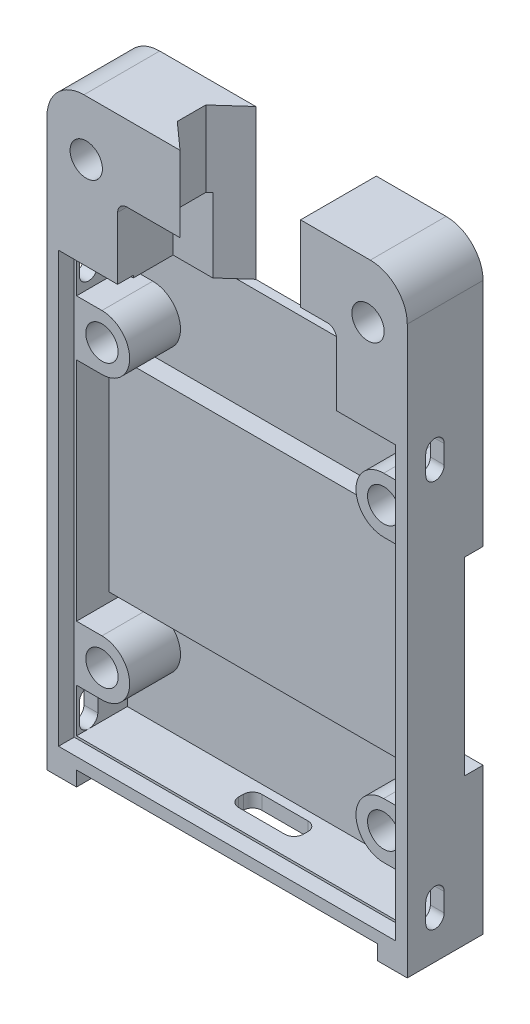
SolidWorks part; units mm, degrees
ref_plane "Front Plane" through (0, 0, 0) normal (0, 0, 1) x (1, 0, 0)
ref_plane "Top Plane" through (0, 0, 0) normal (0, 1, 0) x (1, 0, 0)
ref_plane "Right Plane" through (0, 0, 0) normal (1, 0, 0) x (0, 0, -1)
sketch "Sketch1" plane through (0, 0, 0) normal (0, 0, 1) x (1, 0, 0)
  line L0 (15.25, -20.35) -> (18, -20.35)
  line L1 (-19.5, -32.6) -> (19.5, -32.6)
  line L2 (-19.5, -32.6) -> (-19.5, 31.1)
  line L3 (-19.5, 31.1) -> (19.5, 31.1)
  line L4 (19.5, -32.6) -> (19.5, 31.1)
  line L5 (-15.25, -20.35) -> (-18, -20.35)
  line L6 (15.25, -26.35) -> (18, -26.35)
  line L7 (15.5, 31.1) -> (-15.5, 31.1) construction
  line L8 (-18, -31.1) -> (-18, 29.6)
  line L9 (-18, 29.6) -> (18, 29.6)
  line L10 (18, -31.1) -> (18, 29.6)
  line L11 (-18, -31.1) -> (18, -31.1)
  line L12 (-18, 14.9) -> (18, 14.9)
  line L13 (7.85, 14.9) -> (-4.95, 14.9) construction
  line L14 (-15.25, 4.15) -> (-18, 4.15)
  line L15 (-15.25, 10.15) -> (-18, 10.15)
  line L16 (15.25, 10.15) -> (18, 10.15)
  line L17 (15.25, 4.15) -> (18, 4.15)
  line L18 (-15.25, -26.35) -> (-18, -26.35)
  line L19 (19.5, -34.2) -> (19.5, -18.35) construction
  line L20 (-19.5, -34.2) -> (-19.5, -18.35) construction
  line L21 (15.3, -32.6) -> (-15.3, -32.6) construction
  arc A0 (19.5, 27.1) -> (15.5, 31.1) centre (15.5, 27.1) ccw construction
  arc A1 (-15.5, 31.1) -> (-19.5, 27.1) centre (-15.5, 27.1) ccw construction
  arc A2 (19.5, 27.1) -> (15.5, 31.1) centre (15.5, 27.1) ccw
  arc A3 (-15.5, 31.1) -> (-19.5, 27.1) centre (-15.5, 27.1) ccw
  arc A4 (-15.5, 29.6) -> (-18, 27.1) centre (-15.5, 27.1) ccw
  arc A5 (18, 27.1) -> (15.5, 29.6) centre (15.5, 27.1) ccw
  circle A6 centre (-15.25, -23.35) radius 1.75
  circle A7 centre (15.25, -23.35) radius 1.75
  circle A8 centre (-15.25, 7.15) radius 1.75
  circle A9 centre (15.25, 7.15) radius 1.75
  circle A10 centre (15.25, 25.15) radius 1.75
  circle A11 centre (-15.25, 25.15) radius 1.75
  circle A12 centre (-15.25, -23.35) radius 3
  circle A13 centre (15.25, -23.35) radius 3
  circle A14 centre (15.25, 7.15) radius 3
  circle A15 centre (-15.25, 7.15) radius 3
  point P46 (0, 0)
  point P69 (0, 0)
  point P72 (0, 0)
  dimension "D2" = 1.5
  dimension "D4" = 6
  dimension "D3" = 3.5
  dimension "D1" = 1.5
extrude "Base shape" add sketch "Sketch1" along normal up to surface (8.2 mm away) contours L10 A5 L9 A4 L8 L12 A11 A10 | L3 A3 L2 L1 L4 A2 A15 L8 L9 L10 A14 A13 L11 A12 | A4 L9 L8 | A5 L10 L9 | A15 L15 L8 | A15 L8 A8 | A15 L8 L14 | L8 A15 | A14 L17 L10 | L10 A14 A9 | L10 A14 | A14 L10 L16 | A13 L6 L10 | L10 A13 A7 | L10 A13 | A13 L10 L0 | A12 L8 L18 | A12 L8 A6 | L8 A12 | A12 L5 L8 region at (16.8481, -20.9099, 0) region at (17.3601, -20.8437, 0) region at (17.3601, -25.8563, 0) region at (18.1004, -23.35, 0) region at (17.3601, 4.6437, 0) region at (16.8481, 4.7099, 0) region at (18.1004, 7.15, 0) region at (17.3601, 9.6563, 0) region at (-17.3601, -25.8563, 0) region at (0, 22.1041, 0) region at (-18.1004, -23.35, 0) region at (-17.9169, -23.35, 0) region at (17.4416, 29.0416, 0) region at (-17.3601, -20.8437, 0) region at (-17.3601, 9.6563, 0) region at (-17.4416, 29.0416, 0) region at (-16.8481, 9.5901, 0) region at (-18.1004, 7.15, 0) region at (-17.3601, 4.6437, 0) region at (-18.7531, -2.75, 0)
sketch "Sketch3" plane through (19.5, 0, 0) normal (1, 0, 0) x (0, 0, -1)
  line L1 (0, -18.35) -> (-2, -18.35)
  line L2 (0, -18.35) -> (0, 2.15)
  line L3 (0, 2.15) -> (-2, 2.15)
  line L4 (-2, -18.35) -> (-2, 2.15)
  line L5 (0, -18.35) -> (2, -18.35) construction
  line L6 (0, 2.15) -> (2, 2.15) construction
  line L7 (0, -32.6) -> (0, 27.1) construction
  dimension "D1" = 2
extrude "Strap cut" cut sketch "Sketch3" against normal through all
sketch "Sketch4" plane through (0, 31.1, 0) normal (0, 1, 0) x (1, 0, 0)
  line L2 (7.95, 0) -> (-5.0998, 0)
  line L4 (-15.5, 0) -> (15.5, 0) construction
  line L5 (-15.5, -8.2) -> (15.5, -8.2) construction
  line L6 (7.95, -8.2) -> (-5.0998, -8.2)
  line L12 (7.95, -8.3) -> (7.95, 0.1)
  line L13 (7.95, 0.1) -> (-4.9883, 0.1)
  line L14 (-4.9883, 0.1) -> (-7.95, -2.5553)
  line L15 (-7.95, -2.5553) -> (-7.95, -5.6447)
  line L16 (-7.95, -5.6447) -> (-4.9883, -8.3)
  line L17 (-4.9883, -8.3) -> (7.95, -8.3)
  line L18 (7.95, -8.3) -> (7.95, 0.1)
  line L19 (7.95, 0.1) -> (-4.9883, 0.1)
  line L20 (-4.9883, 0.1) -> (-7.95, -2.5553)
  line L21 (-7.95, -2.5553) -> (-7.95, -5.6447)
  line L22 (-7.95, -5.6447) -> (-4.9883, -8.3)
  line L23 (-4.9883, -8.3) -> (7.95, -8.3)
  dimension "D1" = 0.1
extrude "XT60 cut" cut sketch "Sketch4" against normal up to next contours L21 L22 L18 L20 region at (0.4142, 31.1, 4.1)
sketch "Sketch5" plane through (19.5, 0, 0) normal (1, 0, 0) x (0, 0, -1)
  line L1 (-8.2, -32.6) -> (-8.2, 27.1) construction
  line L2 (-6.2, -31.1) -> (-4.2, -31.1)
  line L3 (-6.2, -31.1) -> (-6.2, -27.1)
  line L4 (-6.2, -27.1) -> (-4.2, -27.1)
  line L5 (-4.2, -31.1) -> (-4.2, -27.1)
  line L6 (-8.2, -31.1) -> (0, -31.1) construction
  line L7 (-8.2, 14.9) -> (0, 14.9) construction
  line L8 (-6.2, 14.9) -> (-4.2, 14.9)
  line L9 (-6.2, 14.9) -> (-6.2, 10.9)
  line L10 (-6.2, 10.9) -> (-4.2, 10.9)
  line L11 (-4.2, 14.9) -> (-4.2, 10.9)
  line L14 (-5.2, -27.1) -> (-5.2, -31.1) construction
  line L15 (-5.2, 14.9) -> (-5.2, 10.9) construction
  circle A0 centre (-5.2, -28.1) radius 1
  circle A1 centre (-5.2, -30.1) radius 1
  circle A2 centre (-5.2, 13.9) radius 1
  circle A3 centre (-5.2, 11.9) radius 1
  point P20 (-5.2, -29.1)
  point P31 (-5.2, 12.9)
  dimension "D3" = 4
  dimension "D1" = 2
  dimension "D2" = 2
extrude "Power wires cut" cut sketch "Sketch5" against normal through all contours A2 | A3 | A3 A2 L9 | A3 L11 A2 | A1 | A0 | A1 L5 A0 | A1 A0 L3 region at (19.5, -30.1, 5.2) region at (19.5, -29.1, 5.9766) region at (19.5, -29.1, 4.4234) region at (19.5, -28.1, 5.2) region at (19.5, 13.9, 5.2) region at (19.5, 12.9, 5.9766) region at (19.5, 12.9, 4.4234) region at (19.5, 11.9, 5.2)
sketch "Sketch6" plane through (0, 0, 8.2) normal (0, 0, 1) x (1, 0, 0)
  line L0 (-7.85, 15.9) -> (-7.85, 21.9) construction
  line L1 (-8.85, 22.9) -> (-10.85, 22.9) construction
  line L2 (-11.85, 15.9) -> (-11.85, 21.9) construction
  line L3 (-8.85, 14.9) -> (-10.85, 14.9) construction
  line L4 (-7.85, 15.9) -> (-7.85, 21.9)
  line L5 (-8.85, 22.9) -> (-10.85, 22.9)
  line L6 (-11.85, 15.9) -> (-11.85, 21.9)
  line L7 (-8.85, 14.9) -> (-10.85, 14.9)
  line L8 (7.85, 15.9) -> (7.85, 21.9) construction
  line L9 (8.85, 22.9) -> (10.85, 22.9) construction
  line L10 (11.85, 15.9) -> (11.85, 21.9) construction
  line L11 (8.85, 14.9) -> (10.85, 14.9) construction
  line L12 (7.85, 15.9) -> (7.85, 21.9)
  line L13 (8.85, 22.9) -> (10.85, 22.9)
  line L14 (11.85, 15.9) -> (11.85, 21.9)
  line L15 (8.85, 14.9) -> (10.85, 14.9)
  line L17 (-11.85, 15.9) -> (-7.85, 15.9)
  line L18 (-11.85, 15.9) -> (-11.85, 14.9)
  line L19 (-11.85, 14.9) -> (-7.85, 14.9)
  line L20 (-7.85, 15.9) -> (-7.85, 14.9)
  line L22 (11.85, 15.9) -> (7.85, 15.9)
  line L23 (11.85, 15.9) -> (11.85, 14.9)
  line L24 (11.85, 14.9) -> (7.85, 14.9)
  line L25 (7.85, 15.9) -> (7.85, 14.9)
  line L26 (-18, 14.9) -> (-5.0998, 14.9) construction
  line L27 (11.85, 21.9) -> (7.85, 21.9)
  line L28 (11.85, 21.9) -> (11.85, 22.9)
  line L29 (11.85, 22.9) -> (7.85, 22.9)
  line L30 (7.85, 21.9) -> (7.85, 22.9)
  line L31 (-8.85, 22.9) -> (7.95, 22.9)
  line L32 (-8.85, 22.9) -> (-8.85, 14.9)
  line L33 (-8.85, 14.9) -> (7.95, 14.9)
  line L34 (7.95, 22.9) -> (7.95, 14.9)
  line L35 (7.95, 14.9) -> (18, 14.9) construction
  line L36 (7.95, 14.9) -> (7.95, 31.1) construction
  arc A0 (-8.85, 14.9) -> (-7.85, 15.9) centre (-8.85, 15.9) ccw construction
  arc A1 (-7.85, 21.9) -> (-8.85, 22.9) centre (-8.85, 21.9) ccw construction
  arc A2 (-10.85, 22.9) -> (-11.85, 21.9) centre (-10.85, 21.9) ccw construction
  arc A3 (-11.85, 15.9) -> (-10.85, 14.9) centre (-10.85, 15.9) ccw construction
  arc A4 (-8.85, 14.9) -> (-7.85, 15.9) centre (-8.85, 15.9) ccw
  arc A5 (-7.85, 21.9) -> (-8.85, 22.9) centre (-8.85, 21.9) ccw
  arc A6 (-10.85, 22.9) -> (-11.85, 21.9) centre (-10.85, 21.9) ccw
  arc A7 (-11.85, 15.9) -> (-10.85, 14.9) centre (-10.85, 15.9) ccw
  arc A8 (8.85, 22.9) -> (7.85, 21.9) centre (8.85, 21.9) ccw construction
  arc A9 (11.85, 21.9) -> (10.85, 22.9) centre (10.85, 21.9) ccw construction
  arc A10 (10.85, 14.9) -> (11.85, 15.9) centre (10.85, 15.9) ccw construction
  arc A11 (7.85, 15.9) -> (8.85, 14.9) centre (8.85, 15.9) ccw construction
  arc A12 (8.85, 22.9) -> (7.85, 21.9) centre (8.85, 21.9) ccw
  arc A13 (11.85, 21.9) -> (10.85, 22.9) centre (10.85, 21.9) ccw
  arc A14 (10.85, 14.9) -> (11.85, 15.9) centre (10.85, 15.9) ccw
  arc A15 (7.85, 15.9) -> (8.85, 14.9) centre (8.85, 15.9) ccw
  line M1 (7.95, 31.1) -> (7.95, 14.9)
  line M15 (-5.0998, 14.9) -> (-5.0998, 31.1)
extrude "IO wires cut" cut sketch "Sketch6" against normal blind 6 contours L33 L25 L12 L30 L31 M15 | A5 L4 L20 L31 M15 | L4 A5 L32 L17 | L5 A6 L6 L17 L32 | A7 L18 | L17 A7 L32 | L32 A4 L17 | A4 L20 | A12 L29 L30 M1 | L27 L12 L22 M1 | L22 A15 M1 | A15 L25 L24 L34 | A15 L34 | A15 A14 L22 M1 | A14 L23 | L14 L27 L22 M1 | L27 A13 L13 A12 L34 | A12 L29 M1 region at (-8.3587, 19.2964, 8.2) region at (-8.4256, 15.4756, 8.2) region at (-6.4903, 18.9365, 8.2) region at (-8.0734, 15.1234, 8.2) region at (-10.2516, 15.4213, 8.2) region at (-10.3368, 19.3662, 8.2) region at (-11.6266, 15.1234, 8.2) region at (1.3751, 18.9, 8.2) region at (7.8959, 15.2606, 8.2) region at (7.8959, 22.5394, 8.2) region at (8.1604, 15.056, 8.2) region at (7.9, 18.9, 8.2) region at (7.9098, 15.7354, 8.2) region at (8.1604, 22.744, 8.2) region at (9.8661, 15.4307, 8.2) region at (9.9, 18.9, 8.2) region at (9.8661, 22.3693, 8.2) region at (11.6266, 15.1234, 8.2)
sketch "Sketch7" plane through (-18, 0, 0) normal (1, 0, 0) x (0, 0, -1)
  line L6 (0, -18.35) -> (0, -20.35)
  line L7 (-2, -18.35) -> (0, -18.35)
  line L8 (-2, 2.15) -> (-2, -18.35)
  line L9 (0, 2.15) -> (-2, 2.15)
  line L12 (0, 3.15) -> (-3, 3.15)
  line L13 (-3, 3.15) -> (-3, -19.35)
  line L14 (-3, -19.35) -> (-1, -19.35)
  line L15 (-1, -19.35) -> (-1, -20.35)
  line L16 (-1, -20.35) -> (0, -20.35)
  line L17 (0, 3.15) -> (-1, 3.15)
  line L19 (0, -31.1) -> (-1, -31.1)
  line L22 (0, -31.1) -> (0, -20.35)
  line L23 (0, -20.35) -> (-1, -20.35)
  line L24 (-1, -31.1) -> (-1, -20.35)
  line L25 (0, 3.15) -> (0, 14.9)
  line L26 (0, 14.9) -> (-1, 14.9)
  line L27 (-1, 3.15) -> (-1, 14.9)
  line L28 (-5.2, 14.9) -> (0, 14.9) construction
  line L31 (0, -20.35) -> (0, -18.35) construction
  line L32 (0, 2.15) -> (-2, 2.15) construction
  line M48 (0, -20.35) -> (0, -18.35)
  line M49 (0, -18.35) -> (-2, -18.35)
  line M50 (-2, -18.35) -> (-2, 2.15)
  line M51 (-2, 2.15) -> (0, 2.15)
  line M52 (0, 2.15) -> (0, 4.15)
  line M53 (0, 4.15) -> (-8.2, 4.15)
  line M55 (-8.2, -20.35) -> (0, -20.35)
  dimension "D1" = 1
extrude "Bottom" add sketch "Sketch7" along normal up to surface (36 mm away) contours L27 L25 L26 M53 | L27 L12 M52 M53 | L14 L15 L12 L13 M55 M48 M49 M50 M51 M52 | L24 L19 L22 M55 region at (-18, -8.5273, 2.2091) region at (-18, -25.725, 0.5) region at (-18, 3.65, 0.5) region at (-18, 9.525, 0.5) up to face at (18, -8.1, 2.55)
sketch "Sketch9" plane through (0, 0, 0) normal (0, 0, -1) x (-1, 0, 0)
  circle A0 centre (-15.25, -23.35) radius 1.75 construction
  circle A1 centre (-15.25, 7.15) radius 1.75 construction
  circle A2 centre (15.25, 7.15) radius 1.75 construction
  circle A3 centre (15.25, -23.35) radius 1.75 construction
  circle A4 centre (-15.25, -23.35) radius 1.75
  circle A5 centre (-15.25, 7.15) radius 1.75
  circle A6 centre (15.25, 7.15) radius 1.75
  circle A7 centre (15.25, -23.35) radius 1.75
extrude "Bottom holes" cut sketch "Sketch9" against normal up to next
sketch "Sketch8" plane through (0, 0, 8.2) normal (0, 0, 1) x (1, 0, 0)
  line L0 (-6.2152, 14.9) -> (-18, 14.9) construction
  line L1 (-18.25, 15.15) -> (18.25, 15.15)
  line L2 (-18.25, 15.15) -> (-18.25, -31.35)
  line L3 (-18.25, -31.35) -> (18.25, -31.35)
  line L4 (18.25, 15.15) -> (18.25, -31.35)
  line L5 (-18, 14.9) -> (-18.25, 14.9) construction
  line L6 (-18, 14.9) -> (-18, 15.15) construction
  line L7 (18, 14.9) -> (18.25, 14.9) construction
  line L8 (-18, -31.1) -> (-18, -31.35) construction
  dimension "D1" = 0.25
extrude "PCB cut" cut sketch "Sketch8" against normal blind 1.7
sketch "Sketch11" plane through (0, -32.6, 0) normal (0, -1, 0) x (1, 0, 0)
  line L0 (19.5, 8.2) -> (19.5, 0) construction
  line L1 (-19.5, 8.2) -> (19.5, 8.2)
  line L2 (-19.5, 8.2) -> (-19.5, -1.8)
  line L3 (-19.5, -1.8) -> (19.5, -1.8)
  line L4 (19.5, 8.2) -> (19.5, -1.8)
  line L5 (-19.5, 3.2) -> (19.5, 3.2) construction
  line L6 (0, -1.8) -> (0, 8.2) construction
  line L8 (-2.5, 4.45) -> (2.5, 4.45)
  line L9 (-3.5, 3.45) -> (-3.5, 2.95)
  line L10 (-2.5, 1.95) -> (2.5, 1.95)
  line L11 (3.5, 3.45) -> (3.5, 2.95)
  line L12 (-3.5, 4.45) -> (3.5, 1.95) construction
  line L13 (-3.5, 1.95) -> (3.5, 4.45) construction
  arc A0 (2.5, 4.45) -> (3.5, 3.45) centre (2.5, 3.45) cw
  arc A1 (2.5, 1.95) -> (3.5, 2.95) centre (2.5, 2.95) ccw
  arc A2 (-3.5, 2.95) -> (-2.5, 1.95) centre (-2.5, 2.95) ccw
  arc A3 (-2.5, 4.45) -> (-3.5, 3.45) centre (-2.5, 3.45) ccw
  point P11 (0, 3.2)
  dimension "D4" = 1
  dimension "D1" = 10
  dimension "D2" = 7
  dimension "D3" = 2.5
extrude "Ledbar wires cut" cut sketch "Sketch11" against normal up to next contours L8 A3 L9 A2 L10 A1 L11 A0 region at (0, -32.6, 3.2)
sketch "Sketch13" plane through (0, -32.6, 0) normal (0, -1, 0) x (1, 0, 0)
  line L0 (-19.5, 8.2) -> (19.5, 8.2) construction
  line L1 (19.5, 0) -> (16.3, 0)
  line L2 (19.5, 0) -> (19.5, 8.2)
  line L3 (19.5, 8.2) -> (16.3, 8.2)
  line L4 (16.3, 0) -> (16.3, 8.2)
  line L5 (16.1, -1.8) -> (16.1, 8.2) construction
  line L6 (0, 8.2) -> (0, 0) construction
  line L7 (-19.5, 0) -> (-16.3, 0)
  line L8 (-19.5, 0) -> (-19.5, 8.2)
  line L9 (-19.5, 8.2) -> (-16.3, 8.2)
  line L10 (-16.3, 0) -> (-16.3, 8.2)
  dimension "D1" = 0.2
extrude "Ledbar sides" add sketch "Sketch13" along normal blind 1.6
sketch "Sketch14" plane through (0, -32.6, 0) normal (0, -1, 0) x (1, 0, 0)
  circle A0 centre (8, 6.85) radius 0.95
  circle A1 centre (-8, 6.85) radius 0.95
  dimension "D1" = 1.9
extrude "Ledbar pressure mounts" add sketch "Sketch14" along normal blind 0.25
sketch "Sketch10" [suppressed] plane through (0, 0, 2) normal (0, 0, -1) x (-1, 0, 0)
  line L0 (0, 2.15) -> (0, -18.35) construction
  line L1 (19.5, 2.15) -> (-19.5, 2.15) construction
  line L2 (19.5, -18.35) -> (-19.5, -18.35) construction
  line L3 (19.5, 2.15) -> (19.5, -18.35) construction
  line L4 (-19.5, 1.15) -> (19.5, 1.15)
  line L5 (-19.5, 1.15) -> (-19.5, 0.65)
  line L6 (-19.5, 0.65) -> (19.5, 0.65)
  line L7 (19.5, 1.15) -> (19.5, 0.65)
  line L8 (-19.5, 1.15) -> (19.5, 0.65) construction
  line L9 (-19.5, 0.65) -> (19.5, 1.15) construction
  line L10 (-19.5, 2.15) -> (19.5, 2.15) construction
  line L11 (-19.5, -1.35) -> (19.5, -1.35)
  line L12 (19.5, -0.85) -> (19.5, -1.35)
  line L13 (-19.5, -0.85) -> (19.5, -0.85)
  line L14 (-19.5, -0.85) -> (-19.5, -1.35)
  line L15 (-19.5, -3.35) -> (19.5, -3.35)
  line L16 (19.5, -2.85) -> (19.5, -3.35)
  line L17 (-19.5, -2.85) -> (19.5, -2.85)
  line L18 (-19.5, -2.85) -> (-19.5, -3.35)
  line L19 (-19.5, -5.35) -> (19.5, -5.35)
  line L20 (19.5, -4.85) -> (19.5, -5.35)
  line L21 (-19.5, -4.85) -> (19.5, -4.85)
  line L22 (-19.5, -4.85) -> (-19.5, -5.35)
  line L23 (-19.5, -7.35) -> (19.5, -7.35)
  line L24 (19.5, -6.85) -> (19.5, -7.35)
  line L25 (-19.5, -6.85) -> (19.5, -6.85)
  line L26 (-19.5, -6.85) -> (-19.5, -7.35)
  line L27 (-19.5, -9.35) -> (19.5, -9.35)
  line L28 (19.5, -8.85) -> (19.5, -9.35)
  line L29 (-19.5, -8.85) -> (19.5, -8.85)
  line L30 (-19.5, -8.85) -> (-19.5, -9.35)
  line L31 (-19.5, -11.35) -> (19.5, -11.35)
  line L32 (19.5, -10.85) -> (19.5, -11.35)
  line L33 (-19.5, -10.85) -> (19.5, -10.85)
  line L34 (-19.5, -10.85) -> (-19.5, -11.35)
  line L35 (-19.5, -13.35) -> (19.5, -13.35)
  line L36 (19.5, -12.85) -> (19.5, -13.35)
  line L37 (-19.5, -12.85) -> (19.5, -12.85)
  line L38 (-19.5, -12.85) -> (-19.5, -13.35)
  line L39 (-19.5, -15.35) -> (19.5, -15.35)
  line L40 (19.5, -14.85) -> (19.5, -15.35)
  line L41 (-19.5, -14.85) -> (19.5, -14.85)
  line L42 (-19.5, -14.85) -> (-19.5, -15.35)
  line L43 (-19.5, -17.35) -> (19.5, -17.35)
  line L44 (19.5, -16.85) -> (19.5, -17.35)
  line L45 (-19.5, -16.85) -> (19.5, -16.85)
  line L46 (-19.5, -16.85) -> (-19.5, -17.35)
  point P6 (0, 0.9)
  dimension "D1" = 1
  dimension "D2" = 0.5
  dimension "D4" = 2
  dimension "D3" = 10
extrude "3D print ribs" [suppressed] add sketch "Sketch10" along normal up to surface (2 mm away) up to face at (13.5, 7.15, 0)
